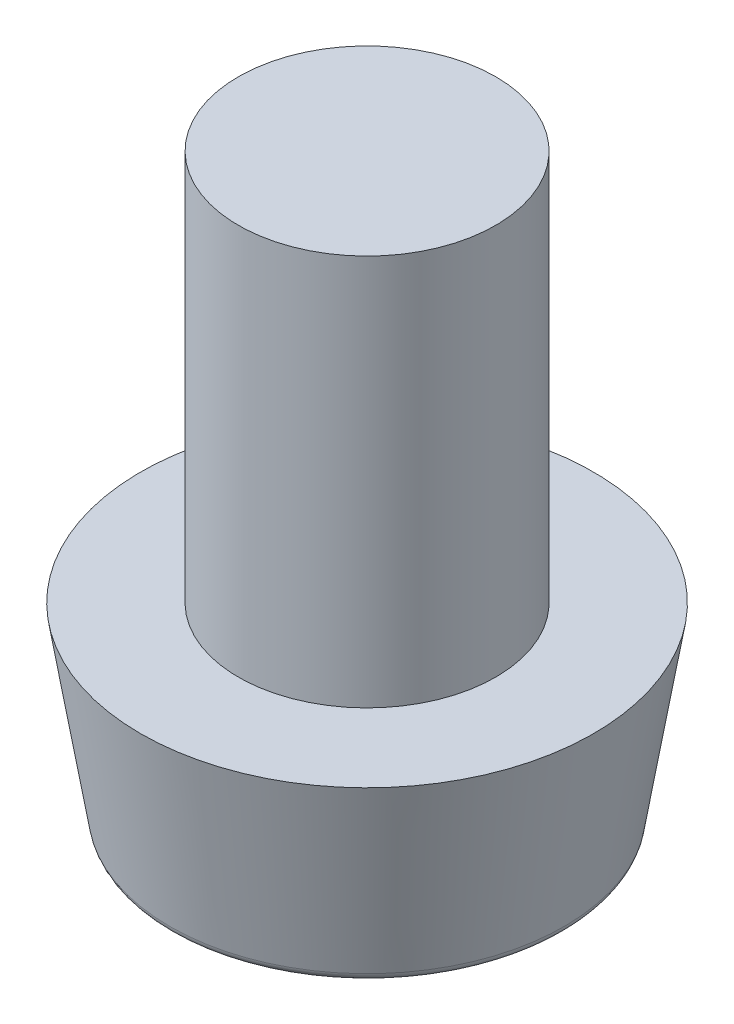
SolidWorks part; units mm, degrees
material "Nylon 101"
ref_plane "Plan de face" through (0, 0, 0) normal (0, 0, 1) x (1, 0, 0)
ref_plane "Plan de dessus" through (0, 0, 0) normal (0, 1, 0) x (1, 0, 0)
ref_plane "Plan de droite" through (0, 0, 0) normal (1, 0, 0) x (0, 0, -1)
sketch "Esquisse1" plane through (0, 0, 0) normal (0, 1, 0) x (1, 0, 0)
  circle A0 centre (0, 0) radius 2.2
  dimension "D1" = 4.4
extrude "Boss.-Extru.1" add sketch "Esquisse1" along normal blind 1.85
sketch "Esquisse2" plane through (0, 1.85, 0) normal (0, 1, 0) x (1, 0, 0)
  circle A0 centre (0, 0) radius 1.25
  dimension "D1" = 2.5
extrude "Boss.-Extru.2" add sketch "Esquisse2" along normal blind 3.8
chamfer "Chanfrein1" distance 0.3 distance2 1.85 1 edges at (0, 0, 2.2) first distance on face at (0, 0, 2.2)
fillet "Congé1" radius 0.1 1 edges at (0, 0, 1.9)
